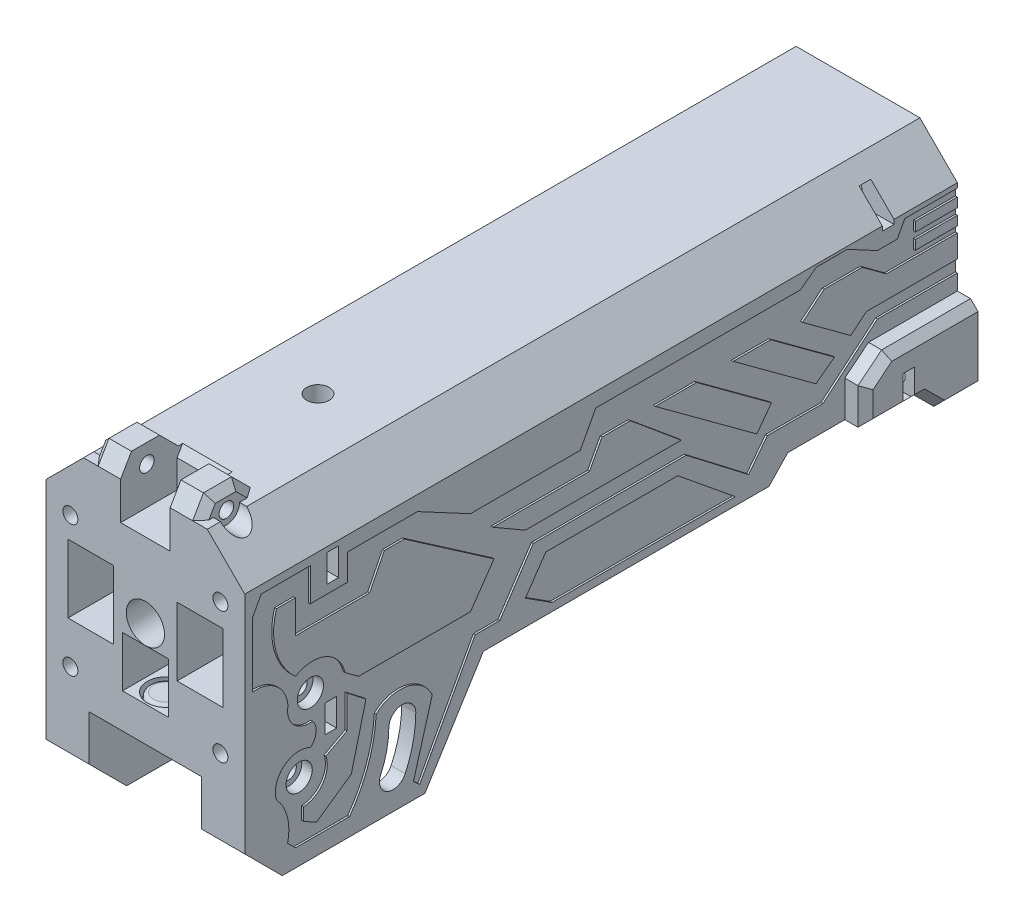
SolidWorks part; units mm, degrees
ref_plane "정면" through (0, 0, 0) normal (0, 0, 1) x (1, 0, 0)
ref_plane "윗면" through (0, 0, 0) normal (0, 1, 0) x (1, 0, 0)
ref_plane "우측면" through (0, 0, 0) normal (1, 0, 0) x (0, 0, -1)
sketch "스케치3" plane through (0, 0, 0) normal (1, 0, 0) x (0, 0, -1)
  line L0 (0, 0) -> (190, 0)
  line L1 (190, 0) -> (190, -55)
  line L2 (190, -55) -> (180.2215, -55)
  line L3 (63.6072, -55) -> (48.0366, -80)
  line L4 (48.0366, -80) -> (0, -80)
  line L5 (0, -80) -> (0, 0)
  line L6 (139.7521, -55) -> (144.7798, -49.7132)
  line L7 (144.7798, -49.7132) -> (174.9094, -49.7132)
  line L8 (174.9094, -49.7132) -> (180.2215, -55)
  line L9 (139.7521, -55) -> (63.6072, -55)
  dimension "D3" = 80
  dimension "D1" = 190
  dimension "D2" = 55
extrude "보스-돌출2" add sketch "스케치3" along normal mid plane 53 contours L5 L4 L3 L2 L1 L0 region at (0, -31.8184, -85.9521)
sketch "스케치6" plane through (0, 0, -190) normal (0, 0, -1) x (-1, 0, 0)
  line L0 (0, 0) -> (0, -30) construction
  line L1 (-26.5, 0) -> (26.5, 0) construction
  circle A0 centre (0, -30) radius 22.575
  dimension "D1" = 45.15
  dimension "D2" = 30
extrude "컷-돌출4" cut sketch "스케치6" against normal blind 160
sketch "스케치4" plane through (0, 0, 0) normal (1, 0, 0) x (0, 0, -1)
  line L1 (30, -30) -> (190, -30)
  line L2 (30, -30) -> (30, -90)
  line L3 (30, -90) -> (190, -90)
  line L4 (190, -30) -> (190, -90)
  dimension "D1" = 30
  dimension "D2" = 30
  dimension "D3" = 60
  dimension "D4" = 160
extrude "컷-돌출2" cut sketch "스케치4" against normal mid plane 45.5
sketch "스케치7" plane through (0, 0, 0) normal (1, 0, 0) x (0, 0, -1)
  circle A0 centre (15, -60) radius 2.05
  dimension "D1" = 4.1
  dimension "D2" = 60
  dimension "D3" = 15
extrude "컷-돌출5" cut sketch "스케치7" against normal through all both and the other way through all
sketch "스케치8" plane through (0, 0, 0) normal (1, 0, 0) x (0, 0, -1)
  line L1 (13.0632, -51.62) -> (100, -51.62)
  line L2 (0, -57.901) -> (0, -86.62)
  line L3 (0, -86.62) -> (100, -86.62)
  line L4 (100, -51.62) -> (100, -86.62)
  line L5 (7.0843, -57.901) -> (0, -57.901)
  arc A0 (13.0632, -51.62) -> (7.0843, -57.901) centre (15.7981, -60.2095) ccw
  dimension "D1" = 51.62
  dimension "D3" = 100
extrude "컷-돌출6" cut sketch "스케치8" against normal mid plane 30
sketch "스케치11" plane through (26.5, 0, 0) normal (1, 0, 0) x (0, 0, -1)
  line L0 (41.3609, -65.8399) -> (15, -60) construction
  arc A0 (42, -60.1) -> (39.5158, -71.3126) centre (14.9961, -59.9987) cw construction
  arc A1 (42.7846, -72.8209) -> (45.6, -60.1135) centre (14.9961, -59.9987) ccw
  arc A2 (36.247, -69.8043) -> (38.4, -60.0865) centre (14.9961, -59.9987) ccw
  arc A3 (36.247, -69.8043) -> (42.7846, -72.8209) centre (39.5158, -71.3126) ccw
  arc A4 (45.6, -60.1135) -> (38.4, -60.0865) centre (42, -60.1) ccw
  point P3 (41.3609, -65.8399)
  dimension "D1" = 3.6
  dimension "D2" = 39.5158
  dimension "D3" = 71.3126
  dimension "D4" = 42
  dimension "D5" = 60.1
  dimension "D6" = 27
extrude "컷-돌출8" cut sketch "스케치11" against normal up to next
mirror "대칭 복사1" about plane through (0, 0, 0) normal (1, 0, 0) of "컷-돌출8"
chamfer "모따기1" distance 10 angle 45 2 edges at (20.75, -80, 0) (-20.75, -80, 0)
chamfer "모따기2" distance 10 angle 45 2 edges at (-26.5, 0, -95) (26.5, 0, -95)
sketch "스케치18" plane through (0, 0, 0) normal (1, 0, 0) x (0, 0, -1)
  circle A0 centre (18, -42) radius 1.95
  dimension "D1" = 3.9
  dimension "D2" = 42
  dimension "D3" = 18
extrude "컷-돌출15" cut sketch "스케치18" against normal through all both and the other way through all
sketch "스케치17" plane through (0, 0, 0) normal (1, 0, 0) x (0, 0, -1)
  line L0 (30, -35.12) -> (30, -32.2)
  line L1 (30, -51.62) -> (23.6487, -51.62)
  line L2 (30, -51.62) -> (30, -46.0645)
  line L3 (30, -32.2) -> (27.7633, -32.2)
  line L4 (23.6487, -51.62) -> (23.6487, -48.62)
  line L5 (23.6487, -48.62) -> (0, -48.62)
  line L6 (30, -46.0645) -> (30, -35.12)
  line L7 (24.5598, -35.12) -> (0, -35.12)
  line L8 (0, -48.62) -> (0, -35.12)
  line L9 (27.7633, -32.2) -> (24.5598, -35.12)
  line L10 (0, -70) -> (0, -10) construction
  dimension "D1" = 16.5
  dimension "D2" = 3
  dimension "D3" = 30
  dimension "D4" = 32.2
extrude "컷-돌출14" cut sketch "스케치17" against normal mid plane 12.2
sketch "스케치19" plane through (0, -48.62, 0) normal (0, 1, 0) x (1, 0, 0)
  line L0 (0, 5.5) -> (0, 0) construction
  line L1 (-6.1, 0) -> (6.1, 0) construction
  circle A0 centre (0, 5.5) radius 5
  circle A1 centre (0, 5.5) radius 4.3
  dimension "D1" = 10
  dimension "D2" = 8.6
  dimension "D3" = 5.5
extrude "컷-돌출16" cut sketch "스케치19" against normal blind 3.5
fillet "필렛1" radius 1 1 edges at (0, -48.62, -1.2)
sketch "스케치20" plane through (0, 0, -30) normal (0, 0, -1) x (-1, 0, 0)
  line L0 (0, 0) -> (0, -91.2285) construction
  line L1 (-20.6469, -20.8712) -> (-8.4469, -20.8712)
  line L2 (-20.6469, -20.8712) -> (-20.6469, -39.0712)
  line L3 (-20.6469, -39.0712) -> (-8.4469, -39.0712)
  line L4 (-8.4469, -20.8712) -> (-8.4469, -39.0712)
  line L5 (-16.5, 0) -> (16.5, 0) construction
  line L6 (8.4469, -20.8712) -> (8.4469, -39.0712)
  line L7 (20.6469, -39.0712) -> (8.4469, -39.0712)
  line L8 (20.6469, -20.8712) -> (20.6469, -39.0712)
  line L9 (20.6469, -20.8712) -> (8.4469, -20.8712)
  arc A0 (22.575, -30) -> (-22.575, -30) centre (0, -30) ccw construction
  dimension "D1" = 12.2
  dimension "D2" = 18.2
extrude "컷-돌출17" cut sketch "스케치20" against normal up to next
sketch "스케치13" plane through (26.5, 0, 0) normal (1, 0, 0) x (0, 0, -1)
  circle A0 centre (15, -60) radius 3.5
  circle A1 centre (18, -42) radius 3.5
  dimension "D1" = 7
  dimension "D2" = 7
extrude "컷-돌출9" cut sketch "스케치13" against normal blind 3.3
sketch "스케치14" plane through (-26.5, 0, 0) normal (-1, 0, 0) x (0, 0, 1)
  line L1 (-10.7853, -60) -> (-12.8927, -56.35)
  line L2 (-12.8927, -56.35) -> (-17.1073, -56.35)
  line L3 (-17.1073, -56.35) -> (-19.2147, -60)
  line L4 (-19.2147, -60) -> (-17.1073, -63.65)
  line L5 (-17.1073, -63.65) -> (-12.8927, -63.65)
  line L6 (-12.8927, -63.65) -> (-10.7853, -60)
  line L7 (-13.7853, -42) -> (-15.8927, -38.35)
  line L8 (-15.8927, -38.35) -> (-20.1073, -38.35)
  line L9 (-20.1073, -38.35) -> (-22.2147, -42)
  line L10 (-22.2147, -42) -> (-20.1073, -45.65)
  line L11 (-20.1073, -45.65) -> (-15.8927, -45.65)
  line L12 (-15.8927, -45.65) -> (-13.7853, -42)
  circle A0 centre (-15, -60) radius 3.65 construction
  circle A1 centre (-18, -42) radius 3.65 construction
  dimension "D1" = 7.3
  dimension "D2" = 7.3
extrude "컷-돌출10" cut sketch "스케치14" against normal blind 3.5
sketch "스케치15" plane through (0, 0, 0) normal (1, 0, 0) x (0, 0, -1)
  circle A0 centre (18.1164, -74.2877) radius 2.1
  dimension "D1" = 4.2
extrude "컷-돌출11" [suppressed] cut sketch "스케치15" against normal through all both and the other way through all
sketch "스케치26" plane through (0, 0, 0) normal (1, 0, 0) x (0, 0, -1)
  line L1 (0, 0) -> (25, 0)
  line L2 (0, 0) -> (0, -25)
  line L3 (0, -25) -> (25, -25)
  line L4 (25, 0) -> (25, -25)
  dimension "D1" = 25
  dimension "D2" = 25
extrude "컷-돌출18" [suppressed] cut sketch "스케치26" against normal mid plane 10
chamfer "모따기3" [suppressed] distance 1 angle 45
sketch "스케치28" plane through (0, 0, 0) normal (0, 0, 1) x (1, 0, 0)
  line L0 (-20, -15) -> (-20, -50) construction
  line L1 (0, 0) -> (0, -69.5439) construction
  circle A0 centre (-20, -15) radius 2
  circle A1 centre (-20, -50) radius 2
  circle A2 centre (20, -50) radius 2
  circle A3 centre (20, -15) radius 2
  dimension "D1" = 4
  dimension "D2" = 4
  dimension "D3" = 15
  dimension "D4" = 35
  dimension "D5" = 20
extrude "컷-돌출20" cut sketch "스케치28" against normal blind 26
ref_plane "평면1" through (0, 0, -25) normal (0, 0, 1) x (1, 0, 0)
sketch "스케치30" plane through (0, 0, -25) normal (0, 0, 1) x (1, 0, 0)
  line L0 (0, 0) -> (0, -77.3775) construction
  line L1 (-15.7565, -15) -> (-17.8782, -11.325)
  line L2 (-17.8782, -11.325) -> (-22.1218, -11.325)
  line L3 (-22.1218, -11.325) -> (-24.2435, -15)
  line L4 (-24.2435, -15) -> (-22.1218, -18.675)
  line L5 (-22.1218, -18.675) -> (-17.8782, -18.675)
  line L6 (-17.8782, -18.675) -> (-15.7565, -15)
  line L7 (-15.7565, -50) -> (-17.8782, -46.325)
  line L8 (-17.8782, -46.325) -> (-22.1218, -46.325)
  line L9 (-22.1218, -46.325) -> (-24.2435, -50)
  line L10 (-24.2435, -50) -> (-22.1218, -53.675)
  line L11 (-22.1218, -53.675) -> (-17.8782, -53.675)
  line L12 (-17.8782, -53.675) -> (-15.7565, -50)
  line L13 (-22.1218, -11.325) -> (-32.6069, -11.325)
  line L14 (-32.6069, -11.325) -> (-32.6069, -18.675)
  line L15 (-32.6069, -18.675) -> (-22.1218, -18.675)
  line L16 (-22.1218, -46.325) -> (-32.6069, -46.325)
  line L17 (-32.6069, -46.325) -> (-32.6069, -53.675)
  line L18 (-32.6069, -53.675) -> (-22.1218, -53.675)
  line L19 (32.6069, -53.675) -> (22.1218, -53.675)
  line L20 (32.6069, -46.325) -> (32.6069, -53.675)
  line L21 (22.1218, -46.325) -> (32.6069, -46.325)
  line L22 (32.6069, -18.675) -> (22.1218, -18.675)
  line L23 (32.6069, -11.325) -> (32.6069, -18.675)
  line L24 (22.1218, -11.325) -> (32.6069, -11.325)
  line L25 (17.8782, -53.675) -> (15.7565, -50)
  line L26 (22.1218, -53.675) -> (17.8782, -53.675)
  line L27 (24.2435, -50) -> (22.1218, -53.675)
  line L28 (22.1218, -46.325) -> (24.2435, -50)
  line L29 (17.8782, -46.325) -> (22.1218, -46.325)
  line L30 (15.7565, -50) -> (17.8782, -46.325)
  line L31 (17.8782, -18.675) -> (15.7565, -15)
  line L32 (22.1218, -18.675) -> (17.8782, -18.675)
  line L33 (24.2435, -15) -> (22.1218, -18.675)
  line L34 (22.1218, -11.325) -> (24.2435, -15)
  line L35 (17.8782, -11.325) -> (22.1218, -11.325)
  line L36 (15.7565, -15) -> (17.8782, -11.325)
  circle A0 centre (-20, -15) radius 3.675 construction
  circle A1 centre (-20, -50) radius 3.675 construction
  circle A2 centre (20, -50) radius 3.675 construction
  circle A3 centre (20, -15) radius 3.675 construction
  dimension "D1" = 7.35
  dimension "D2" = 7.35
extrude "컷-돌출21" cut sketch "스케치30" along normal blind 3.1 contours L14 L15 L4 L3 L13 | L5 L6 L1 L2 L3 L4 | L17 L18 L10 L9 L16 | L11 L12 L7 L8 L9 L10 | L30 L25 L26 L27 L28 L29 | L21 L28 L27 L19 L20 | L36 L31 L32 L33 L34 L35 | L24 L34 L33 L22 L23 region at (-20, -15, -25) region at (-27.8748, -15, -25) region at (-20, -50, -25) region at (-27.8748, -50, -25) region at (27.8748, -50, -25) region at (20, -50, -25) region at (27.8748, -15, -25) region at (20, -15, -25)
sketch "스케치32" plane through (26.5, 0, 0) normal (1, 0, 0) x (0, 0, -1)
  line L0 (190, -35) -> (166.3004, -35)
  line L1 (190, -10) -> (190, -55) construction
  line L2 (166.3004, -35) -> (160, -40.0972)
  line L3 (160, -40.0972) -> (160, -49.7132)
  line L4 (144.7798, -49.7132) -> (174.9094, -49.7132) construction
  line L5 (160, -49.7132) -> (174.9094, -49.7132)
  line L6 (174.9094, -49.7132) -> (180.2215, -55)
  line L7 (180.2215, -55) -> (190, -55)
  line L8 (190, -55) -> (190, -35)
  dimension "D1" = 30
  dimension "D2" = 20
extrude "보스-돌출3" add sketch "스케치32" along normal blind 5.5
chamfer "모따기4" distance 2 angle 45 6 edges at (32, -35, -178.1502) (32, -37.5486, -163.1502) (32, -55, -185.1107) (32, -52.3566, -177.5655) (32, -49.7132, -167.4547) (32, -44.9052, -160)
mirror "대칭 복사2" about plane through (0, 0, 0) normal (1, 0, 0) of "모따기4", "보스-돌출3"
sketch "스케치31" plane through (0, 0, -190) normal (0, 0, -1) x (-1, 0, 0)
  line L0 (0, 0) -> (0, -71.295) construction
  line L1 (-16.5, 0) -> (16.5, 0) construction
  circle A0 centre (-16, -7.5) radius 2
  circle A1 centre (16, -7.5) radius 2
  circle A2 centre (-27.5, -45) radius 2
  circle A3 centre (27.5, -45) radius 2
  dimension "D1" = 4
  dimension "D4" = 4
  dimension "D2" = 16
  dimension "D3" = 7.5
  dimension "D5" = 45
  dimension "D6" = 27.5
extrude "컷-돌출22" cut sketch "스케치31" against normal blind 21
ref_plane "평면2" through (0, 0, -170) normal (0, 0, -1) x (-1, 0, 0)
sketch "스케치33" plane through (0, 0, -170) normal (0, 0, -1) x (-1, 0, 0)
  line L0 (-18.1218, -3.825) -> (-30.1482, -3.825)
  line L1 (-11.7565, -7.5) -> (-13.8782, -3.825)
  line L2 (-13.8782, -3.825) -> (-18.1218, -3.825)
  line L3 (-18.1218, -3.825) -> (-20.2435, -7.5)
  line L4 (-20.2435, -7.5) -> (-18.1218, -11.175)
  line L5 (-18.1218, -11.175) -> (-13.8782, -11.175)
  line L6 (-13.8782, -11.175) -> (-11.7565, -7.5)
  line L7 (-23.2565, -45) -> (-25.3782, -41.325)
  line L8 (-25.3782, -41.325) -> (-29.6218, -41.325)
  line L9 (-29.6218, -41.325) -> (-31.7435, -45)
  line L10 (-31.7435, -45) -> (-29.6218, -48.675)
  line L11 (-29.6218, -48.675) -> (-25.3782, -48.675)
  line L12 (-25.3782, -48.675) -> (-23.2565, -45)
  line L13 (0, 0) -> (0, -77.1299) construction
  line L14 (34.8567, -48.675) -> (29.6218, -48.675)
  line L15 (34.8567, -41.325) -> (34.8567, -48.675)
  line L16 (29.6218, -41.325) -> (34.8567, -41.325)
  line L17 (30.1482, -11.175) -> (18.1218, -11.175)
  line L18 (30.1482, -3.825) -> (30.1482, -11.175)
  line L19 (25.3782, -48.675) -> (23.2565, -45)
  line L20 (29.6218, -48.675) -> (25.3782, -48.675)
  line L21 (31.7435, -45) -> (29.6218, -48.675)
  line L22 (29.6218, -41.325) -> (31.7435, -45)
  line L23 (25.3782, -41.325) -> (29.6218, -41.325)
  line L24 (23.2565, -45) -> (25.3782, -41.325)
  line L25 (-30.1482, -3.825) -> (-30.1482, -11.175)
  line L26 (-30.1482, -11.175) -> (-18.1218, -11.175)
  line L27 (-29.6218, -41.325) -> (-34.8567, -41.325)
  line L28 (-34.8567, -41.325) -> (-34.8567, -48.675)
  line L29 (-34.8567, -48.675) -> (-29.6218, -48.675)
  line L30 (13.8782, -11.175) -> (11.7565, -7.5)
  line L31 (18.1218, -11.175) -> (13.8782, -11.175)
  line L32 (20.2435, -7.5) -> (18.1218, -11.175)
  line L33 (18.1218, -3.825) -> (20.2435, -7.5)
  line L34 (13.8782, -3.825) -> (18.1218, -3.825)
  line L35 (11.7565, -7.5) -> (13.8782, -3.825)
  line L36 (18.1218, -3.825) -> (30.1482, -3.825)
  circle A0 centre (-16, -7.5) radius 3.675 construction
  circle A1 centre (-27.5, -45) radius 3.675 construction
  circle A2 centre (27.5, -45) radius 3.675 construction
  circle A3 centre (16, -7.5) radius 3.675 construction
  dimension "D1" = 7.35
  dimension "D3" = 7.35
extrude "컷-돌출23" cut sketch "스케치33" along normal blind 3.1 contours L25 L26 L4 L3 L0 | L5 L6 L1 L2 L3 L4 | L28 L29 L10 L9 L27 | L11 L12 L7 L8 L9 L10 | L24 L19 L20 L21 L22 L23 | L16 L22 L21 L14 L15 | L35 L30 L31 L32 L33 L34 | L36 L33 L32 L17 L18 region at (24.6483, -7.5, -170) region at (16, -7.5, -170) region at (27.5, -45, -170) region at (32.7247, -45, -170) region at (-32.7247, -45, -170) region at (-27.5, -45, -170) region at (-24.6483, -7.5, -170) region at (-16, -7.5, -170)
sketch "스케치34" plane through (20.6469, 0, 0) normal (-1, 0, 0) x (0, 0, 1)
  line L0 (-27.5, -25) -> (-24, -25) construction
  line L1 (-27.5, -22.85) -> (-24, -22.85)
  line L2 (-27.5, -27.15) -> (-24, -27.15)
  arc A0 (-27.5, -22.85) -> (-27.5, -27.15) centre (-27.5, -25) ccw
  arc A1 (-24, -27.15) -> (-24, -22.85) centre (-24, -25) ccw
  point P2 (-25.75, -25)
  dimension "D1" = 2.15
  dimension "D2" = 25
  dimension "D3" = 27.5
  dimension "D4" = 3.5
extrude "컷-돌출24" cut sketch "스케치34" against normal blind 0.5
sketch "스케치35" plane through (26.5, 0, 0) normal (1, 0, 0) x (0, 0, -1)
  line L0 (4.3788, -12.1605) -> (17.4588, -12.1605)
  line L1 (17.4588, -12.1605) -> (17.4588, -20.9598)
  line L2 (17.4588, -20.9598) -> (27.3283, -20.9598)
  line L3 (27.3283, -20.9598) -> (27.3283, -13.9442)
  line L4 (27.3283, -13.9442) -> (46.0304, -13.9442)
  line L5 (46.0304, -13.9442) -> (60.1749, -21.5079)
  line L6 (60.1749, -21.5079) -> (89.4552, -21.5079)
  line L7 (89.4552, -21.5079) -> (93.5746, -13.8044)
  line L8 (93.5746, -13.8044) -> (148.1762, -13.8044)
  line L9 (148.1762, -13.8044) -> (152.3739, -10.7015)
  line L10 (152.3739, -10.7015) -> (160.6503, -10.7015)
  line L11 (160.6503, -10.7015) -> (168.6712, -14.9907)
  line L12 (168.6712, -14.9907) -> (173.9859, -14.9907)
  line L13 (173.9859, -14.9907) -> (175.9845, -11.2531)
  line L14 (175.9845, -11.2531) -> (190, -11.2531)
  line L15 (190, -10) -> (190, -35) construction
  line L16 (4.3788, -12.1605) -> (2.1225, -16.38)
  line L17 (2.1225, -16.38) -> (2.1225, -33.6027)
  line L18 (11.4114, -73.213) -> (13.5254, -75.327)
  line L19 (13.5254, -75.327) -> (27.9388, -75.327)
  line L20 (49.9898, -58.1918) -> (44.975, -75.758)
  line L21 (44.975, -75.758) -> (46.6409, -77.244)
  line L22 (46.6409, -77.244) -> (61.4347, -50.0704)
  line L23 (61.4347, -50.0704) -> (68.0042, -50.0704)
  line L24 (68.0042, -50.0704) -> (76.9141, -36.7465)
  line L25 (76.9141, -36.7465) -> (117.6568, -36.7465)
  line L26 (117.6568, -36.7465) -> (134.3365, -49.5594)
  line L27 (134.3365, -49.5594) -> (139.3266, -43.0633)
  line L28 (139.3266, -43.0633) -> (154.152, -43.0633)
  line L29 (154.152, -43.0633) -> (168.6712, -30.8147)
  line L30 (168.6712, -30.8147) -> (190, -30.8147)
  line L31 (74.8102, -48.3354) -> (80.2823, -40.3748)
  line L32 (80.2823, -40.3748) -> (115.4636, -40.3748)
  line L33 (115.4636, -40.3748) -> (130.7898, -52.8762)
  line L34 (130.7898, -52.8762) -> (81.9216, -52.8762)
  line L35 (81.9216, -52.8762) -> (74.8102, -48.3354)
  line L36 (8.4554, -17.5947) -> (13.5254, -17.5947)
  line L37 (13.5254, -17.5947) -> (13.5254, -26.3718)
  line L38 (13.5254, -26.3718) -> (33.2932, -26.3718)
  line L39 (33.2932, -26.3718) -> (37.1999, -18.5335)
  line L40 (37.1999, -18.5335) -> (42.516, -18.5335)
  line L41 (42.516, -18.5335) -> (66.4479, -35.0709)
  line L42 (66.4479, -35.0709) -> (60.1749, -44.1487)
  line L43 (60.1749, -44.1487) -> (30.3536, -44.1487)
  line L44 (30.3536, -44.1487) -> (26.7207, -41.4707)
  line L45 (21.6567, -58.1918) -> (27.2544, -55.2013)
  line L46 (27.2544, -55.2013) -> (27.2544, -46.4611)
  line L47 (27.2544, -46.4611) -> (32.3126, -50.3727)
  line L48 (32.3126, -50.3727) -> (28.401, -65.7495)
  line L49 (28.401, -65.7495) -> (19.0939, -72.224)
  line L50 (19.0939, -72.224) -> (15.6544, -70.2685)
  line L51 (15.6544, -70.2685) -> (15.6544, -66.8961)
  line L52 (116.3715, -26.4574) -> (136.5424, -41.2783)
  line L53 (136.5424, -41.2783) -> (140.4107, -36.0136)
  line L54 (140.4107, -36.0136) -> (120.4517, -21.3483)
  line L55 (120.4517, -21.3483) -> (109.4183, -21.3483)
  line L56 (109.4183, -21.3483) -> (116.3715, -26.4574)
  line L57 (130.2267, -21.3483) -> (140.1837, -21.3483)
  line L58 (140.1837, -21.3483) -> (157.2241, -33.8692)
  line L59 (157.2241, -33.8692) -> (152.2853, -37.5563)
  line L60 (152.2853, -37.5563) -> (130.2267, -21.3483)
  line L61 (148.6888, -21.5873) -> (154.4591, -16.825)
  line L62 (154.4591, -16.825) -> (164.5979, -16.825)
  line L63 (164.5979, -16.825) -> (171.0792, -21.5873)
  line L64 (171.0792, -21.5873) -> (190, -21.5873)
  line L65 (190, -21.5873) -> (190, -27.6087)
  line L66 (190, -27.6087) -> (165.7445, -27.6087)
  line L67 (165.7445, -27.6087) -> (161.5713, -31.053)
  line L68 (161.5713, -31.053) -> (148.6888, -21.5873)
  line L69 (95.2544, -21.3483) -> (102.8001, -21.3483)
  line L70 (102.8001, -21.3483) -> (116.3715, -32.6296)
  line L71 (116.3715, -32.6296) -> (74.8102, -32.6296)
  line L72 (74.8102, -32.6296) -> (66.1345, -27.6087)
  line L73 (66.1345, -27.6087) -> (91.9067, -27.6087)
  line L74 (91.9067, -27.6087) -> (95.2544, -21.3483)
  line L76 (190, -15.7941) -> (178.7897, -15.7941)
  line L77 (190, -15.7941) -> (190, -13.2941)
  line L78 (190, -13.2941) -> (178.7897, -13.2941)
  line L79 (178.7897, -15.7941) -> (178.7897, -13.2941)
  line L80 (190, -19.9969) -> (178.7897, -19.9969)
  line L81 (190, -19.9969) -> (190, -17.4969)
  line L82 (190, -17.4969) -> (178.7897, -17.4969)
  line L83 (178.7897, -19.9969) -> (178.7897, -17.4969)
  arc A0 (2.1225, -33.6027) -> (11.5293, -41.4707) centre (2.8919, -42.2401) cw
  arc A1 (11.5293, -41.4707) -> (18.0693, -48.3354) centre (17.1839, -42.6312) ccw
  arc A2 (18.0693, -48.3354) -> (17.5299, -54.1868) centre (14.8739, -50.9914) cw
  arc A3 (17.5299, -54.1868) -> (8.4554, -61.7293) centre (14.5296, -59.8072) ccw
  arc A4 (8.4554, -61.7293) -> (11.4114, -73.213) centre (-0.9339, -70.2685) cw
  arc A5 (27.9388, -75.327) -> (35.0371, -55.2013) centre (-2.1134, -53.4129) ccw
  arc A6 (35.0371, -55.2013) -> (49.9898, -58.1918) centre (41.4076, -62.2255) cw
  arc A7 (13.5254, -35.7464) -> (26.7207, -41.4707) centre (18.0832, -43.3106) cw
  arc A8 (13.5254, -35.7464) -> (8.4554, -17.5947) centre (25.0912, -22.732) cw
  arc A9 (21.6567, -58.1918) -> (15.6544, -66.8961) centre (15.4065, -60.3034) cw
  line M27 (190, -35) -> (190, -10)
  dimension "D1" = 2.5
  dimension "D2" = 2.5
extrude "컷-돌출25" cut sketch "스케치35" against normal blind 0.5 contours A5 A6 L20 L21 L22 L23 L24 L25 L26 L27 L28 L29 L30 L66 L67 L68 L61 L62 L63 L64 L14 L13 L12 L11 L10 L9 L8 L7 L6 L5 L4 L3 L2 L1 L0 L16 L17 A0 A1 A2 A3 A4 L18 L19 A9 L45 L46 L47 M27 | L35 L34 L33 L32 L31 region at (26.5, -34.1911, -81.9729) region at (26.5, -46.9814, -100.6653)
mirror "대칭 복사3" about plane through (0, 0, 0) normal (1, 0, 0) of "컷-돌출25"
sketch "스케치36" plane through (0, 0, 0) normal (0, 0, 1) x (1, 0, 0)
  line L0 (0, 0) -> (0, -30) construction
  line L1 (16.5, 0) -> (-16.5, 0) construction
  circle A0 centre (0, -30) radius 2.05
  dimension "D1" = 4.1
  dimension "D2" = 30
extrude "컷-돌출26" cut sketch "스케치36" against normal through all
sketch "스케치37" plane through (0, 0, 0) normal (0, 0, 1) x (1, 0, 0)
  circle A0 centre (0, -30) radius 5.1
  dimension "D1" = 10.2
extrude "컷-돌출27" cut sketch "스케치37" against normal blind 21
sketch "스케치38" plane through (0, 0, 0) normal (1, 0, 0) x (0, 0, -1)
  line L2 (24, -22.85) -> (27.5, -22.85) construction
  line L3 (27.5, -27.15) -> (24, -27.15) construction
  line L4 (23.9, -34.5) -> (27.7, -34.5) construction
  line L5 (23.9, -32.4) -> (27.7, -32.4)
  line L6 (23.9, -36.6) -> (27.7, -36.6)
  arc A2 (24, -22.85) -> (24, -27.15) centre (24, -25) ccw construction
  arc A3 (27.5, -27.15) -> (27.5, -22.85) centre (27.5, -25) ccw construction
  arc A4 (23.9, -32.4) -> (23.9, -36.6) centre (23.9, -34.5) ccw
  arc A5 (27.7, -36.6) -> (27.7, -32.4) centre (27.7, -34.5) ccw
  point P8 (23.9, -34.5)
  point P9 (25.8, -34.5)
  dimension "D1" = 9.5
  dimension "D2" = 2.1
  dimension "D3" = 3.8
  dimension "D4" = 0.2
  dimension "D5" = 23.9
  dimension "D6" = 34.5
extrude "컷-돌출28" cut sketch "스케치38" against normal mid plane 24
sketch "스케치39" plane through (-26.5, 0, 0) normal (-1, 0, 0) x (0, 0, 1)
  circle A0 centre (-24, -25) radius 3.55 construction
  circle A1 centre (-23.9, -34.5) radius 3.55
  dimension "D1" = 7.1
  dimension "D2" = 7.1
extrude "컷-돌출29" cut sketch "스케치39" against normal blind 7
sketch "스케치40" plane through (-26.5, 0, 0) normal (-1, 0, 0) x (0, 0, 1)
  line L0 (-13.5254, -26.3718) -> (-33.2932, -26.3718) construction
  line L1 (-13.5254, -26.3718) -> (-33.2932, -26.3718) construction
  line L2 (-13.5254, -26.3718) -> (-33.2932, -26.3718) construction
  line L3 (-29.2555, -26.3718) -> (-18.8009, -26.3718) construction
  line L4 (-17.4588, -20.9598) -> (-27.3283, -20.9598) construction
  line L5 (-27.3283, -20.9598) -> (-21.1596, -20.9598) construction
  arc A0 (-29.2555, -26.3718) -> (-18.8009, -26.3718) centre (-24.0282, -24.8854) ccw construction
  arc A1 (-27.3283, -20.9598) -> (-21.1596, -20.9598) centre (-24.244, -25.5543) cw construction
  arc A2 (-19.739, -34.6359) -> (-25.4828, -38.4901) centre (-23.5458, -35.1698) cw
  arc A3 (-13.5254, -35.7464) -> (-20.3609, -34.7781) centre (-18.0832, -43.3106) ccw construction
  arc A4 (-25.0347, -37.8638) -> (-26.7207, -41.4707) centre (-18.0832, -43.3106) ccw construction
  arc A5 (-25.4828, -38.4901) -> (-19.739, -34.6359) centre (-24.1442, -34.278) cw
  arc A6 (-25.0347, -37.8638) -> (-26.7207, -41.4707) centre (-18.0832, -43.3106) ccw construction
extrude "컷-돌출30" cut sketch "스케치40" against normal blind 0.5
sketch "스케치41" plane through (0, 0, 0) normal (1, 0, 0) x (0, 0, -1)
  line L0 (15, 0) -> (16.534, 0)
  line L1 (0, 0) -> (15, 0)
  line L2 (0, 0) -> (0, -10.03)
  line L3 (0, -10.03) -> (15.05, -10.03)
  line L4 (15.05, -2.5703) -> (15.05, -10.03)
  line L5 (0, 0) -> (190, 0) construction
  line L6 (16.534, 0) -> (15.05, -2.5703)
  dimension "D1" = 10.03
  dimension "D2" = 15
  dimension "D3" = 15.05
  dimension "D4" = 60
extrude "컷-돌출31" cut sketch "스케치41" against normal mid plane 13.2
sketch "스케치43" plane through (-6.6, 0, 0) normal (1, 0, 0) x (0, 0, -1)
  line L0 (0, 0) -> (2.8868, 5)
  line L1 (2.8868, 5) -> (10.3561, 5)
  line L2 (10.3561, 5) -> (15.3561, 0)
  line L3 (0, 0) -> (190, 0) construction
  line L4 (15.3561, 0) -> (0, 0)
  dimension "D1" = 5
  dimension "D2" = 135
  dimension "D3" = 60
extrude "보스-돌출4" add sketch "스케치43" against normal blind 8
mirror "대칭 복사4" about plane through (0, 0, 0) normal (1, 0, 0) of "보스-돌출4"
sketch "스케치44" plane through (0, 0, 0) normal (1, 0, 0) x (0, 0, -1)
  circle A0 centre (7, 0) radius 1.95
  dimension "D1" = 3.9
  dimension "D2" = 7
  dimension "D3" = 0
extrude "컷-돌출32" cut sketch "스케치44" against normal through all both and the other way through all
sketch "스케치45" plane through (14.6, 0, 0) normal (1, 0, 0) x (0, 0, -1)
  circle A0 centre (7, 0) radius 3.5
  dimension "D1" = 7
extrude "컷-돌출33" cut sketch "스케치45" along normal through all
sketch "스케치46" plane through (-14.6, 0, 0) normal (-1, 0, 0) x (0, 0, 1)
  line L1 (-2.7853, 0) -> (-4.8927, 3.65)
  line L2 (-4.8927, 3.65) -> (-9.1073, 3.65)
  line L3 (-9.1073, 3.65) -> (-11.2147, 0)
  line L4 (-11.2147, 0) -> (-9.1073, -3.65)
  line L5 (-9.1073, -3.65) -> (-4.8927, -3.65)
  line L6 (-4.8927, -3.65) -> (-2.7853, 0)
  circle A0 centre (-7, 0) radius 3.65 construction
  dimension "D1" = 7.3
extrude "컷-돌출34" cut sketch "스케치46" along normal through all
sketch "스케치47" plane through (0, 0, 0) normal (0, 1, 0) x (1, 0, 0)
  line L0 (0, 46.015) -> (0, 0) construction
  circle A0 centre (0, 46.015) radius 3
  dimension "D1" = 6
  dimension "D2" = 46.015
extrude "컷-돌출35" cut sketch "스케치47" against normal blind 5.1
chamfer "모따기5" distance 2 angle 45 6 edges at (-14.6, 2.5, -12.8561) (-14.6, 5, -6.6214) (14.6, 2.5, -12.8561) (14.6, 5, -6.6214) (14.6, 2.5, -1.4434)
